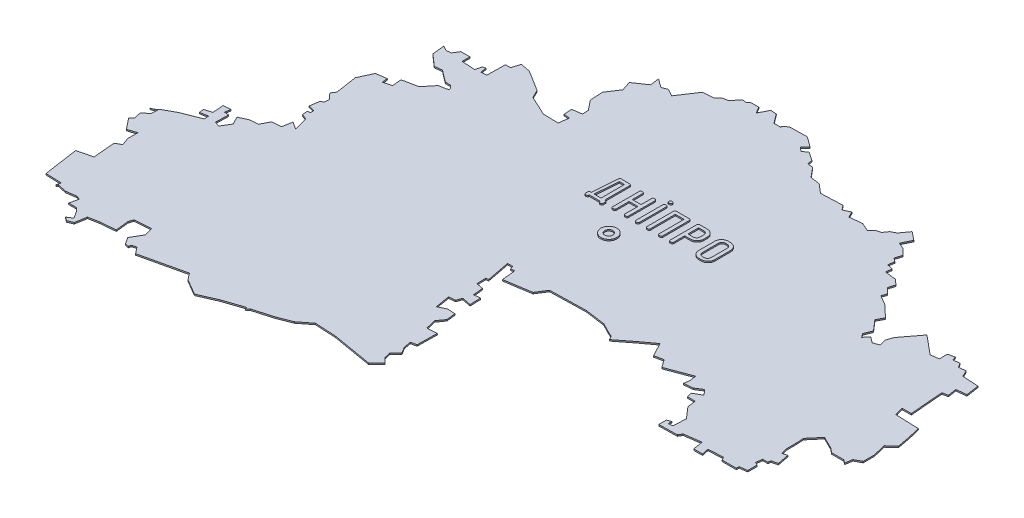
SolidWorks part; units mm, degrees
ref_plane "Спереди" through (0, 0, 0) normal (0, 0, 1) x (1, 0, 0)
ref_plane "Сверху" through (0, 0, 0) normal (0, 1, 0) x (1, 0, 0)
ref_plane "Справа" through (0, 0, 0) normal (1, 0, 0) x (0, 0, -1)
sketch "Эскиз1" plane through (0, 0, 0) normal (0, 1, 0) x (1, 0, 0)
  circle A0 centre (6738.8776, -4880.9525) radius 636.7007
  line B0 (2348.5221, -465.2874) -> (2324.4937, -467.8832)
  line B1 (2324.4937, -467.8832) -> (2319.3223, -454.2434)
  line B2 (2319.3223, -454.2434) -> (2295.2939, -459.4479)
  line B3 (2295.2939, -459.4479) -> (2295.2939, -489.9457)
  line B4 (2295.2939, -489.9457) -> (2264.8062, -493.8573)
  line B5 (2264.8062, -493.8573) -> (2194.6895, -435.4474)
  line B6 (2194.6895, -435.4474) -> (2141.4867, -505.526)
  line B7 (2141.4867, -505.526) -> (2133.059, -530.8371)
  line B8 (2133.059, -530.8371) -> (2140.1989, -554.8503)
  line B9 (2140.1989, -554.8503) -> (2118.1466, -563.2755)
  line B10 (2118.1466, -563.2755) -> (2095.4136, -546.4099)
  line B11 (2095.4136, -546.4099) -> (2080.5115, -565.244)
  line B12 (2080.5115, -565.244) -> (2070.1254, -551.5889)
  line B13 (2070.1254, -551.5889) -> (2081.7891, -522.384)
  line B14 (2081.7891, -522.384) -> (2048.0376, -483.4611)
  line B15 (2048.0376, -483.4611) -> (2061.6901, -457.5073)
  line B16 (2061.6901, -457.5073) -> (2016.8768, -415.3179)
  line B17 (2016.8768, -415.3179) -> (1981.2102, -394.5661)
  line B18 (1981.2102, -394.5661) -> (1988.3603, -375.7422)
  line B19 (1988.3603, -375.7422) -> (1967.5856, -354.9599)
  line B20 (1967.5856, -354.9599) -> (1974.7357, -331.6173)
  line B21 (1974.7357, -331.6173) -> (1955.9041, -314.0837)
  line B22 (1955.9041, -314.0837) -> (1913.0696, -308.9021)
  line B23 (1913.0696, -308.9021) -> (1916.3157, -286.8371)
  line B24 (1916.3157, -286.8371) -> (1894.238, -281.6352)
  line B25 (1894.238, -281.6352) -> (1897.4943, -258.2799)
  line B26 (1897.4943, -258.2799) -> (1883.8951, -247.9015)
  line B27 (1883.8951, -247.9015) -> (1892.3051, -221.935)
  line B28 (1892.3051, -221.935) -> (1868.9498, -199.8802)
  line B29 (1868.9498, -199.8802) -> (1846.2422, -189.5069)
  line B30 (1846.2422, -189.5069) -> (1863.786, -153.8021)
  line B31 (1863.786, -153.8021) -> (1832.5821, -128.4961)
  line B32 (1832.5821, -128.4961) -> (1809.2369, -160.9395)
  line B33 (1809.2369, -160.9395) -> (1790.413, -170.6778)
  line B34 (1790.413, -170.6778) -> (1778.0483, -188.1937)
  line B35 (1778.0483, -188.1937) -> (1759.2954, -193.3981)
  line B36 (1759.2954, -193.3981) -> (1744.3602, -208.3156)
  line B37 (1744.3602, -208.3156) -> (1713.1995, -194.6808)
  line B38 (1713.1995, -194.6808) -> (1667.1442, -199.8802)
  line B39 (1667.1442, -199.8802) -> (1656.7302, -177.8051)
  line B40 (1656.7302, -177.8051) -> (1631.4064, -189.5069)
  line B41 (1631.4064, -189.5069) -> (1617.8098, -172.6209)
  line B42 (1617.8098, -172.6209) -> (1537.3299, -175.8417)
  line B43 (1537.3299, -175.8417) -> (1503.6063, -147.32)
  line B44 (1503.6063, -147.32) -> (1467.8939, -142.1257)
  line B45 (1467.8939, -142.1257) -> (1438.7017, -106.4336)
  line B46 (1438.7017, -106.4336) -> (1417.9474, -104.4677)
  line B47 (1417.9474, -104.4677) -> (1414.6911, -85.6717)
  line B48 (1414.6911, -85.6717) -> (1382.2096, -63.6118)
  line B49 (1382.2096, -63.6118) -> (1365.3745, -77.2236)
  line B50 (1365.3745, -77.2236) -> (1349.7966, -63.6118)
  line B51 (1349.7966, -63.6118) -> (1366.6775, -44.7904)
  line B52 (1366.6775, -44.7904) -> (1329.6544, -17.5184)
  line B53 (1329.6544, -17.5184) -> (1264.7854, -18.8316)
  line B54 (1264.7854, -18.8316) -> (1247.2848, -31.7983)
  line B55 (1247.2848, -31.7983) -> (1249.2177, -36.3449)
  line B56 (1249.2177, -36.3449) -> (1223.2462, -36.3449)
  line B57 (1223.2462, -36.3449) -> (1197.9326, -1.9507)
  line B58 (1197.9326, -1.9507) -> (1175.8879, 0)
  line B59 (1175.8879, 0) -> (1157.0665, -36.3449)
  line B60 (1157.0665, -36.3449) -> (1143.4242, -12.3419)
  line B61 (1143.4242, -12.3419) -> (1112.9112, -12.3419)
  line B62 (1112.9112, -12.3419) -> (1102.5429, -20.7645)
  line B63 (1102.5429, -20.7645) -> (1088.9183, -18.8316)
  line B64 (1088.9183, -18.8316) -> (1064.8975, -48.0212)
  line B65 (1064.8975, -48.0212) -> (1044.1661, -51.2597)
  line B66 (1044.1661, -51.2597) -> (1029.2563, -66.8528)
  line B67 (1029.2563, -66.8528) -> (989.6246, -68.7883)
  line B68 (989.6246, -68.7883) -> (943.5541, -138.2319)
  line B69 (943.5541, -138.2319) -> (916.2948, -123.3068)
  line B70 (916.2948, -123.3068) -> (896.1857, -131.7422)
  line B71 (896.1857, -131.7422) -> (863.6965, -107.7189)
  line B72 (863.6965, -107.7189) -> (868.2711, -142.1257)
  line B73 (868.2711, -142.1257) -> (820.9051, -174.564)
  line B74 (820.9051, -174.564) -> (832.5714, -210.2663)
  line B75 (832.5714, -210.2663) -> (802.0914, -256.347)
  line B76 (802.0914, -256.347) -> (805.3476, -304.3479)
  line B77 (805.3476, -304.3479) -> (834.5475, -341.3354)
  line B78 (834.5475, -341.3354) -> (835.8327, -364.048)
  line B79 (835.8327, -364.048) -> (800.1406, -369.2423)
  line B80 (800.1406, -369.2423) -> (802.0914, -399.7503)
  line B81 (802.0914, -399.7503) -> (824.1614, -401.033)
  line B82 (824.1614, -401.033) -> (818.9798, -438.6809)
  line B83 (818.9798, -438.6809) -> (762.5055, -437.3804)
  line B84 (762.5055, -437.3804) -> (689.1757, -402.9939)
  line B85 (689.1757, -402.9939) -> (674.2379, -372.4885)
  line B86 (674.2379, -372.4885) -> (597.0321, -324.4698)
  line B87 (597.0321, -324.4698) -> (552.8945, -316.0344)
  line B88 (552.8945, -316.0344) -> (560.6923, -317.3476)
  line B89 (560.6923, -317.3476) -> (550.926, -348.4804)
  line B90 (550.926, -348.4804) -> (532.1376, -348.4804)
  line B91 (532.1376, -348.4804) -> (530.8244, -416.621)
  line B92 (530.8244, -416.621) -> (510.0777, -418.5717)
  line B93 (510.0777, -418.5717) -> (506.8316, -396.5042)
  line B94 (506.8316, -396.5042) -> (496.4608, -397.7869)
  line B95 (496.4608, -397.7869) -> (489.9609, -421.8102)
  line B96 (489.9609, -421.8102) -> (439.994, -418.5717)
  line B97 (439.994, -418.5717) -> (439.994, -389.3642)
  line B98 (439.994, -389.3642) -> (406.2425, -389.3642)
  line B99 (406.2425, -389.3642) -> (392.6027, -411.4317)
  line B100 (392.6027, -411.4317) -> (375.1174, -413.3825)
  line B101 (375.1174, -413.3825) -> (356.2528, -402.9939)
  line B102 (356.2528, -402.9939) -> (361.475, -449.0669)
  line B103 (361.475, -449.0669) -> (404.2918, -486.7097)
  line B104 (404.2918, -486.7097) -> (431.5511, -483.4611)
  line B105 (431.5511, -483.4611) -> (476.3186, -517.2177)
  line B106 (476.3186, -517.2177) -> (495.1578, -517.2177)
  line B107 (472.4425, -543.1892) -> (441.9194, -580.8167)
  line B108 (441.9194, -580.8167) -> (385.4602, -592.4804)
  line B109 (385.4602, -592.4804) -> (388.6886, -626.8745)
  line B110 (388.6886, -626.8745) -> (358.2213, -635.3277)
  line B111 (358.2213, -635.3277) -> (356.2528, -614.5403)
  line B112 (356.2528, -614.5403) -> (317.3298, -619.7346)
  line B113 (317.3298, -619.7346) -> (293.309, -670.9816)
  line B114 (293.309, -670.9816) -> (305.6204, -751.4692)
  line B115 (305.6204, -751.4692) -> (295.2699, -768.3551)
  line B116 (295.2699, -768.3551) -> (315.3969, -790.3997)
  line B117 (315.3969, -790.3997) -> (314.0837, -807.2704)
  line B118 (314.0837, -807.2704) -> (303.7129, -814.3951)
  line B119 (303.7129, -814.3951) -> (298.5059, -848.8096)
  line B120 (298.5059, -848.8096) -> (322.5444, -855.3171)
  line B121 (322.5444, -855.3171) -> (322.5444, -868.934)
  line B122 (322.5444, -868.934) -> (312.1406, -868.934)
  line B123 (312.1406, -868.934) -> (314.0837, -889.061)
  line B124 (314.0837, -889.061) -> (334.1903, -897.4963)
  line B125 (334.1903, -897.4963) -> (347.8352, -948.7383)
  line B126 (347.8352, -948.7383) -> (320.5505, -931.23)
  line B127 (320.5505, -931.23) -> (314.0837, -967.5876)
  line B128 (314.0837, -967.5876) -> (279.6845, -970.8159)
  line B129 (279.6845, -970.8159) -> (262.8392, -1003.239)
  line B130 (262.8392, -1003.239) -> (233.614, -1004.5319)
  line B131 (233.614, -1004.5319) -> (199.8878, -1020.1529)
  line B132 (199.8878, -1020.1529) -> (214.79, -1049.3273)
  line B133 (214.79, -1049.3273) -> (194.6808, -1083.0509)
  line B134 (194.6808, -1083.0509) -> (175.8594, -1076.5841)
  line B135 (175.8594, -1076.5841) -> (177.1625, -1028.5628)
  line B136 (177.1625, -1028.5628) -> (160.3019, -1027.2751)
  line B137 (160.3019, -1027.2751) -> (163.5481, -1006.5106)
  line B138 (163.5481, -1006.5106) -> (136.271, -1008.4537)
  line B139 (136.271, -1008.4537) -> (139.5171, -1049.3273)
  line B140 (139.5171, -1049.3273) -> (112.2782, -1057.7982)
  line B141 (112.2782, -1057.7982) -> (114.2035, -1074.6511)
  line B142 (114.2035, -1074.6511) -> (143.4211, -1069.4619)
  line B143 (143.4211, -1069.4619) -> (144.7063, -1086.9727)
  line B144 (144.7063, -1086.9727) -> (75.2907, -1114.2218)
  line B145 (75.2907, -1114.2218) -> (32.4561, -1138.2324)
  line B146 (32.4561, -1138.2324) -> (24.0106, -1146.6601)
  line B147 (24.0106, -1146.6601) -> (8.4353, -1153.16)
  line B148 (8.4353, -1153.16) -> (29.2354, -1144.7424)
  line B149 (29.2354, -1144.7424) -> (27.2847, -1168.7277)
  line B150 (27.2847, -1168.7277) -> (5.2248, -1187.5592)
  line B151 (5.2248, -1187.5592) -> (11.6992, -1214.7906)
  line B152 (11.6992, -1214.7906) -> (0, -1225.1766)
  line B153 (0, -1225.1766) -> (32.4561, -1266.0605)
  line B154 (32.4561, -1266.0605) -> (64.9122, -1255.6642)
  line B155 (64.9122, -1255.6642) -> (64.9122, -1293.335)
  line B156 (64.9122, -1293.335) -> (75.2907, -1322.545)
  line B157 (75.2907, -1322.545) -> (54.516, -1334.1909)
  line B158 (54.516, -1334.1909) -> (61.6382, -1415.9738)
  line B159 (61.6382, -1415.9738) -> (6.5024, -1429.6161)
  line B160 (6.5024, -1429.6161) -> (25.306, -1559.3949)
  line B161 (25.306, -1559.3949) -> (85.0113, -1561.3202)
  line B162 (85.0113, -1561.3202) -> (78.5266, -1585.3689)
  line B163 (78.5266, -1585.3689) -> (80.4621, -1577.5534)
  line B164 (80.4621, -1577.5534) -> (85.0113, -1573.0296)
  line B165 (85.0113, -1573.0296) -> (119.4105, -1580.1797)
  line B166 (119.4105, -1580.1797) -> (157.038, -1574.9727)
  line B167 (157.038, -1574.9727) -> (170.6626, -1580.1797)
  line B168 (170.6626, -1580.1797) -> (163.5481, -1612.6181)
  line B169 (163.5481, -1612.6181) -> (192.7479, -1612.6181)
  line B170 (192.7479, -1612.6181) -> (208.3511, -1629.4786)
  line B171 (208.3511, -1629.4786) -> (221.9477, -1651.5486)
  line B172 (221.9477, -1651.5486) -> (203.1441, -1663.9032)
  line B173 (203.1441, -1663.9032) -> (216.7687, -1673.6009)
  line B174 (216.7687, -1673.6009) -> (236.8601, -1665.163)
  line B175 (236.8601, -1665.163) -> (243.9899, -1622.9863)
  line B176 (243.9899, -1622.9863) -> (281.6454, -1615.854)
  line B177 (281.6454, -1615.854) -> (339.4253, -1610.6826)
  line B178 (339.4253, -1610.6826) -> (334.1903, -1562.641)
  line B179 (334.1903, -1562.641) -> (339.4253, -1544.4775)
  line B180 (339.4253, -1544.4775) -> (401.0457, -1540.5379)
  line B181 (401.0457, -1540.5379) -> (409.4734, -1573.0296)
  line B182 (409.4734, -1573.0296) -> (385.4602, -1613.9033)
  line B183 (385.4602, -1613.9033) -> (401.0457, -1637.9063)
  line B184 (401.0457, -1637.9063) -> (414.6525, -1641.1702)
  line B185 (414.6525, -1641.1702) -> (417.9341, -1631.4115)
  line B186 (417.9341, -1631.4115) -> (433.484, -1627.5533)
  line B187 (433.484, -1627.5533) -> (452.2978, -1651.5486)
  line B188 (452.2978, -1651.5486) -> (615.8636, -1613.9033)
  line B189 (615.8636, -1613.9033) -> (634.685, -1637.9063)
  line B190 (634.685, -1637.9063) -> (693.0517, -1672.3309)
  line B191 (693.0517, -1672.3309) -> (759.2771, -1643.0676)
  line B192 (759.2771, -1643.0676) -> (834.5475, -1617.8403)
  line B193 (834.5475, -1617.8403) -> (850.1228, -1691.1168)
  line B194 (850.1228, -1691.1168) -> (835.8327, -1624.3071)
  line B195 (835.8327, -1624.3071) -> (846.2112, -1615.854)
  line B196 (846.2112, -1615.854) -> (918.2557, -1595.0895)
  line B197 (918.2557, -1595.0895) -> (969.5078, -1574.9727)
  line B198 (969.5078, -1574.9727) -> (1013.6175, -1540.5379)
  line B199 (1013.6175, -1540.5379) -> (1092.1822, -1544.4775)
  line B200 (1092.1822, -1544.4775) -> (1240.7646, -1569.7835)
  line B201 (1240.7646, -1569.7835) -> (1273.2461, -1539.2781)
  line B202 (1273.2461, -1539.2781) -> (1254.4069, -1520.4567)
  line B203 (1254.4069, -1520.4567) -> (1249.2177, -1498.4044)
  line B204 (1249.2177, -1498.4044) -> (1271.2776, -1474.4014)
  line B205 (1271.2776, -1474.4014) -> (1257.6378, -1452.3237)
  line B206 (1257.6378, -1452.3237) -> (1252.4562, -1424.4193)
  line B207 (1252.4562, -1424.4193) -> (1273.2461, -1419.8778)
  line B208 (1273.2461, -1419.8778) -> (1274.5237, -1345.9079)
  line B209 (1274.5237, -1345.9079) -> (1237.5286, -1347.851)
  line B210 (1237.5286, -1347.851) -> (1228.4431, -1308.8849)
  line B211 (1228.4431, -1308.8849) -> (1247.2848, -1282.9489)
  line B212 (1247.2848, -1282.9489) -> (1245.9538, -1269.332)
  line B213 (1245.9538, -1269.332) -> (1243.9955, -1249.2076)
  line B214 (1243.9955, -1249.2076) -> (1214.8109, -1247.2822)
  line B215 (1214.8109, -1247.2822) -> (1186.2587, -1260.8712)
  line B216 (1186.2587, -1260.8712) -> (1177.1757, -1206.373)
  line B217 (1177.1757, -1206.373) -> (1201.1787, -1204.4401)
  line B218 (1201.1787, -1204.4401) -> (1208.311, -1184.3029)
  line B219 (1208.311, -1184.3029) -> (1242.0778, -1190.8053)
  line B220 (1242.0778, -1190.8053) -> (1240.7646, -1149.9139)
  line B221 (1240.7646, -1149.9139) -> (1216.7464, -1153.16)
  line B222 (1216.7464, -1153.16) -> (1213.5155, -1115.5426)
  line B223 (1213.5155, -1115.5426) -> (1187.5719, -1110.9833)
  line B224 (1187.5719, -1110.9833) -> (1186.2587, -1076.5841)
  line B225 (1186.2587, -1076.5841) -> (1195.9793, -1074.6511)
  line B226 (1195.9793, -1074.6511) -> (1179.1188, -987.6892)
  line B227 (1179.1188, -987.6892) -> (1197.9326, -987.6892)
  line B228 (1197.9326, -987.6892) -> (1203.1294, -1000.0082)
  line B229 (1203.1294, -1000.0082) -> (1216.7464, -998.0651)
  line B230 (1216.7464, -998.0651) -> (1221.9356, -1049.3273)
  line B231 (1221.9356, -1049.3273) -> (1269.3269, -1042.195)
  line B232 (1269.3269, -1042.195) -> (1320.579, -1033.7597)
  line B233 (1320.579, -1033.7597) -> (1344.5719, -996.1143)
  line B234 (1344.5719, -996.1143) -> (1479.5754, -992.8682)
  line B235 (1479.5754, -992.8682) -> (1554.8407, -1003.239)
  line B236 (1554.8407, -1003.239) -> (1587.312, -1020.1529)
  line B237 (1587.312, -1020.1529) -> (1609.3821, -1030.5212)
  line B238 (1609.3821, -1030.5212) -> (1615.8667, -1044.1457)
  line B239 (1615.8667, -1044.1457) -> (1672.3335, -1000.0082)
  line B240 (1672.3335, -1000.0082) -> (1723.578, -962.3628)
  line B241 (1723.578, -962.3628) -> (1750.8525, -1013.6581)
  line B242 (1750.8525, -1013.6581) -> (1783.2476, -1006.5106)
  line B243 (1783.2476, -1006.5106) -> (1804.0629, -1035.7206)
  line B244 (1804.0629, -1035.7206) -> (1896.1913, -1001.3036)
  line B245 (1896.1913, -1001.3036) -> (1899.445, -1027.2751)
  line B246 (1899.445, -1027.2751) -> (1896.1913, -1047.3741)
  line B247 (1896.1913, -1047.3741) -> (1929.9834, -1044.1457)
  line B248 (1929.9834, -1044.1457) -> (1955.9041, -1027.2751)
  line B249 (1955.9041, -1027.2751) -> (1972.757, -1047.3741)
  line B250 (1972.757, -1047.3741) -> (1942.2618, -1064.8848)
  line B251 (1942.2618, -1064.8848) -> (1947.4688, -1083.0509)
  line B252 (1947.4688, -1083.0509) -> (1976.0209, -1083.0509)
  line B253 (1976.0209, -1083.0509) -> (1979.9249, -1114.2218)
  line B254 (1979.9249, -1114.2218) -> (2016.8768, -1157.0538)
  line B255 (2016.8768, -1157.0538) -> (2013.6409, -1204.4401)
  line B256 (2013.6409, -1204.4401) -> (1998.1088, -1206.373)
  line B257 (1998.1088, -1206.373) -> (1998.1088, -1192.7484)
  line B258 (1998.1088, -1192.7484) -> (1983.1533, -1197.9199)
  line B259 (1983.1533, -1197.9199) -> (1983.1533, -1226.472)
  line B260 (1983.1533, -1226.472) -> (2051.3116, -1225.1766)
  line B261 (2051.3116, -1225.1766) -> (2059.747, -1211.5698)
  line B262 (2059.747, -1211.5698) -> (2121.3674, -1203.1345)
  line B263 (2121.3674, -1203.1345) -> (2127.8774, -1240.1245)
  line B264 (2127.8774, -1240.1245) -> (2160.3335, -1240.1245)
  line B265 (2160.3335, -1240.1245) -> (2155.1087, -1214.7906)
  line B266 (2155.1087, -1214.7906) -> (2210.2978, -1211.5698)
  line B267 (2210.2978, -1211.5698) -> (2216.7748, -1223.2538)
  line B268 (2216.7748, -1223.2538) -> (2270.0209, -1223.2538)
  line B269 (2270.0209, -1223.2538) -> (2270.0209, -1212.8576)
  line B270 (2270.0209, -1212.8576) -> (2298.54, -1208.9892)
  line B271 (2298.54, -1208.9892) -> (2298.54, -1173.9524)
  line B272 (2298.54, -1173.9524) -> (2286.8661, -1168.7277)
  line B273 (2286.8661, -1168.7277) -> (2290.1046, -1144.7424)
  line B274 (2290.1046, -1144.7424) -> (2308.9083, -1144.7424)
  line B275 (2308.9083, -1144.7424) -> (2310.8514, -1134.3462)
  line B276 (2310.8514, -1134.3462) -> (2332.9468, -1129.1494)
  line B277 (2332.9468, -1129.1494) -> (2324.4937, -1085.0296)
  line B278 (2324.4937, -1085.0296) -> (2306.9753, -1090.2188)
  line B279 (2306.9753, -1090.2188) -> (2300.5263, -1064.8848)
  line B280 (2300.5263, -1064.8848) -> (2300.5263, -1030.5212)
  line B281 (2300.5263, -1030.5212) -> (2298.54, -1001.3036)
  line B282 (2298.54, -1001.3036) -> (2334.8721, -958.4715)
  line B283 (2334.8721, -958.4715) -> (2380.9528, -981.1766)
  line B284 (2380.9528, -981.1766) -> (2397.8057, -994.8189)
  line B285 (2397.8057, -994.8189) -> (2443.8864, -994.8189)
  line B286 (2443.8864, -994.8189) -> (2455.6288, -1004.5319)
  line B287 (2455.6288, -1004.5319) -> (2459.4896, -977.2828)
  line B288 (2459.4896, -977.2828) -> (2484.7779, -963.6862)
  line B289 (2484.7779, -963.6862) -> (2484.7779, -921.4993)
  line B290 (2484.7779, -921.4993) -> (2473.132, -874.1232)
  line B291 (2473.132, -874.1232) -> (2501.6587, -848.8096)
  line B292 (2501.6587, -848.8096) -> (2491.9178, -797.5422)
  line B293 (2491.9178, -797.5422) -> (2481.5571, -754.7153)
  line B294 (2481.5571, -754.7153) -> (2394.5672, -751.4692)
  line B295 (2394.5672, -751.4692) -> (2385.4943, -719.0308)
  line B296 (2385.4943, -719.0308) -> (2419.9266, -719.0308)
  line B297 (2419.9266, -719.0308) -> (2413.4166, -643.73)
  line B298 (2413.4166, -643.73) -> (2409.5151, -594.4184)
  line B299 (2409.5151, -594.4184) -> (2430.2618, -590.5475)
  line B300 (2430.2618, -590.5475) -> (2425.0726, -558.0913)
  line B301 (2425.0726, -558.0913) -> (2462.7078, -553.5447)
  line B302 (2462.7078, -553.5447) -> (2455.6288, -505.526)
  line B303 (2455.6288, -505.526) -> (2395.8906, -502.2672)
  line B304 (2395.8906, -502.2672) -> (2384.2167, -478.2337)
  line B305 (2384.2167, -478.2337) -> (2358.2351, -481.5078)
  line B306 (2358.2351, -481.5078) -> (2348.5221, -465.2874)
  spline B307 degree 2 poles (495.1578, -517.2177) (518.5054, -534.731) (495.1578, -537.9644) knots 0.345161 0.345161 0.345161 0.348387 0.348387 0.348387
  spline B308 degree 2 poles (495.1578, -537.9644) (471.137, -541.2461) (472.4425, -543.1892) knots 0.348387 0.348387 0.348387 0.351613 0.351613 0.351613
sketch_block_instance "Блок16-1"
sketch_block "Блок16"
extrude "Бобышка-Вытянуть4" add sketch "Эскиз1" along normal blind 5 contours B307 B308 B107 B108 B109 B110 B111 B112 B113 B114 B115 B116 B117 B118 B119 B120 B121 B122 B123 B124 B125 B126 B127 B128 B129 B130 B131 B132 B133 B134 B135 B136 B137 B138 B139 B140 B141 B142 B143 B144 B145 B146 B147 B148 B149 B150 B151 B152 B153 B154 B155 region at (1166.6437, 0, 842.1844)
sketch "Эскиз2" plane through (0, 0, 0) normal (0, 1, 0) x (1, 0, 0)
  line L0 (1093.834, -618.2958) -> (1676.9971, -618.2958) construction
  circle A0 centre (1274.3707, -704.4029) radius 15
  circle A1 centre (1274.3707, -704.4029) radius 30
  text T0 "<b>ДНІПРО</b>" font "GOST Type AU" height 110
  dimension "D1" = 30
  dimension "D2" = 60
extrude "Бобышка-Вытянуть5" add sketch "Эскиз2" along normal blind 10
scale "Масштаб1" scale about centroid uniform scaling yes scale factor 0.05
